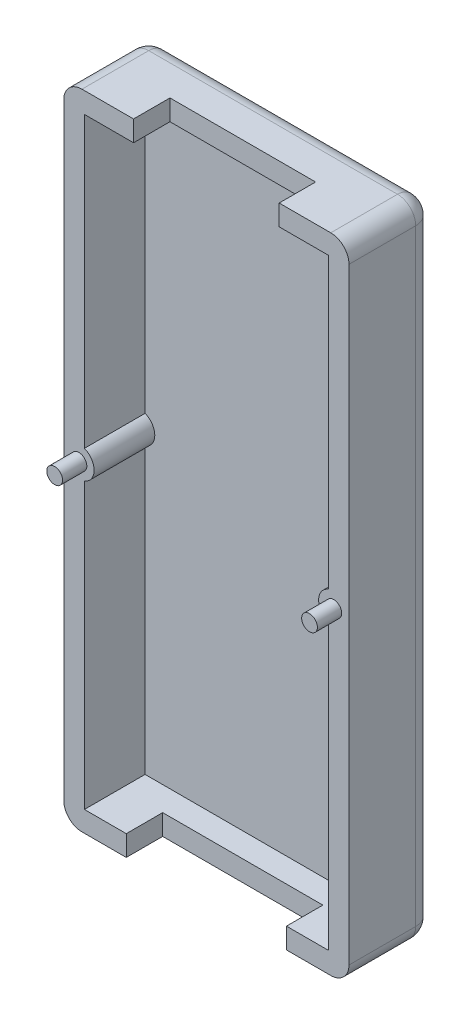
SolidWorks part; units mm, degrees
ref_plane "前视基准面" through (0, 0, 0) normal (0, 0, 1) x (1, 0, 0)
ref_plane "上视基准面" through (0, 0, 0) normal (0, 1, 0) x (1, 0, 0)
ref_plane "右视基准面" through (0, 0, 0) normal (1, 0, 0) x (0, 0, -1)
other "Configuration Table"
sketch "草图1" plane through (0, 0, 0) normal (0, 0, 1) x (1, 0, 0)
  line L1 (0, 0) -> (23.5, 0)
  line L2 (0, 0) -> (0, -53)
  line L3 (0, -53) -> (23.5, -53)
  line L4 (23.5, 0) -> (23.5, -53)
  line L5 (1.7, -1.7) -> (21.8, -1.7)
  line L6 (1.7, -1.7) -> (1.7, -51.3)
  line L7 (1.7, -51.3) -> (21.8, -51.3)
  line L8 (21.8, -1.7) -> (21.8, -51.3)
  circle A0 centre (1.25, -26.7) radius 1.25
  circle A1 centre (22.25, -26.7) radius 1.25
  dimension "D7" = 2.5
  dimension "D8" = 2.5
  dimension "D10" = 25
  dimension "D1" = 23.5
  dimension "D2" = 53
  dimension "D3" = 1.7
  dimension "D4" = 1.7
  dimension "D5" = 1.7
  dimension "D6" = 1.7
  dimension "D9" = 25
extrude "凸台-拉伸1" add sketch "草图1" along normal blind 7 contours A1 L4 L1 L2 A0 L6 L5 L8 | L6 A0 | A1 L8 L7 L6 A0 L2 L3 L4 | A1 L8 region at (11.75, -0.3557, 0) region at (0.3434, -28.0216, 0) region at (0.9525, -26.7, 0) region at (22.5475, -26.7, 0)
extrude "凸台-拉伸2" add sketch "草图1<5>" along normal blind 7 contours A0 | A1
sketch "草图1<5>" plane through (0, 0, 0) normal (0, 0, 1) x (1, 0, 0) same geometry as "草图1"
extrude "凸台-拉伸3" add sketch "草图1<6>" along normal blind 2 contours A1 L8 L5 L6 A0 L7 region at (11.75, -26.4995, 0)
sketch "草图1<6>" plane through (0, 0, 0) normal (0, 0, 1) x (1, 0, 0) same geometry as "草图1"
sketch "草图2" plane through (0, 0, 7) normal (0, 0, 1) x (1, 0, 0)
  line L0 (1.7, -51.3) -> (21.8, -51.3) construction
  line L1 (5.15, -51.3) -> (18.35, -51.3)
  line L2 (5.15, -51.3) -> (5.15, -53)
  line L3 (5.15, -53) -> (18.35, -53)
  line L4 (18.35, -51.3) -> (18.35, -53)
  line L5 (0, -53) -> (23.5, -53) construction
  line L6 (0, 0) -> (23.5, 0) construction
  line L7 (5.75, 0) -> (17.75, 0)
  line L8 (5.75, 0) -> (5.75, -1.7)
  line L9 (5.75, -1.7) -> (17.75, -1.7)
  line L10 (17.75, 0) -> (17.75, -1.7)
  line L11 (1.7, -1.7) -> (21.8, -1.7) construction
  line L12 (0, 0) -> (0, -53) construction
  circle A5 centre (1.25, -26.7) radius 0.65
  circle A8 centre (22.25, -26.7) radius 0.65
  arc A11 (1.7, -27.8662) -> (1.7, -25.5338) centre (1.25, -26.7) ccw construction
  arc A12 (21.8, -25.5338) -> (21.8, -27.8662) centre (22.25, -26.7) ccw construction
  line M9 (21.8, -51.3) -> (1.7, -51.3)
  line M13 (1.7, -1.7) -> (21.8, -1.7)
  line M14 (0, -53) -> (23.5, -53)
  line M16 (23.5, 0) -> (0, 0)
  dimension "D1" = 1.3
  dimension "D2" = 1.3
  dimension "D3" = 0
  dimension "D4" = 0
  dimension "D5" = 13.2
  dimension "D6" = 12
  dimension "D7" = 5.75
  dimension "D8" = 5.15
extrude "切除-拉伸1" cut sketch "草图2" against normal blind 3 contours L4 L2 M9 M14 | L10 L8 M16 M13 region at (11.75, -52.15, 7) region at (11.75, -0.85, 7)
extrude "凸台-拉伸4" add sketch "草图2<3>" along normal blind 2 contours A8 | A5 region at (22.25, -26.7, 7)
sketch "草图2<3>" plane through (0, 0, 7) normal (0, 0, 1) x (1, 0, 0) same geometry as "草图2"
fillet "圆角1" radius 1.5 8 edges at (11.75, 0, 0) (0, -26.5, 0) (11.75, -53, 0) (23.5, -26.5, 0) (0, 0, 3.5) (23.5, 0, 3.5) (23.5, -53, 3.5) (0, -53, 3.5)
